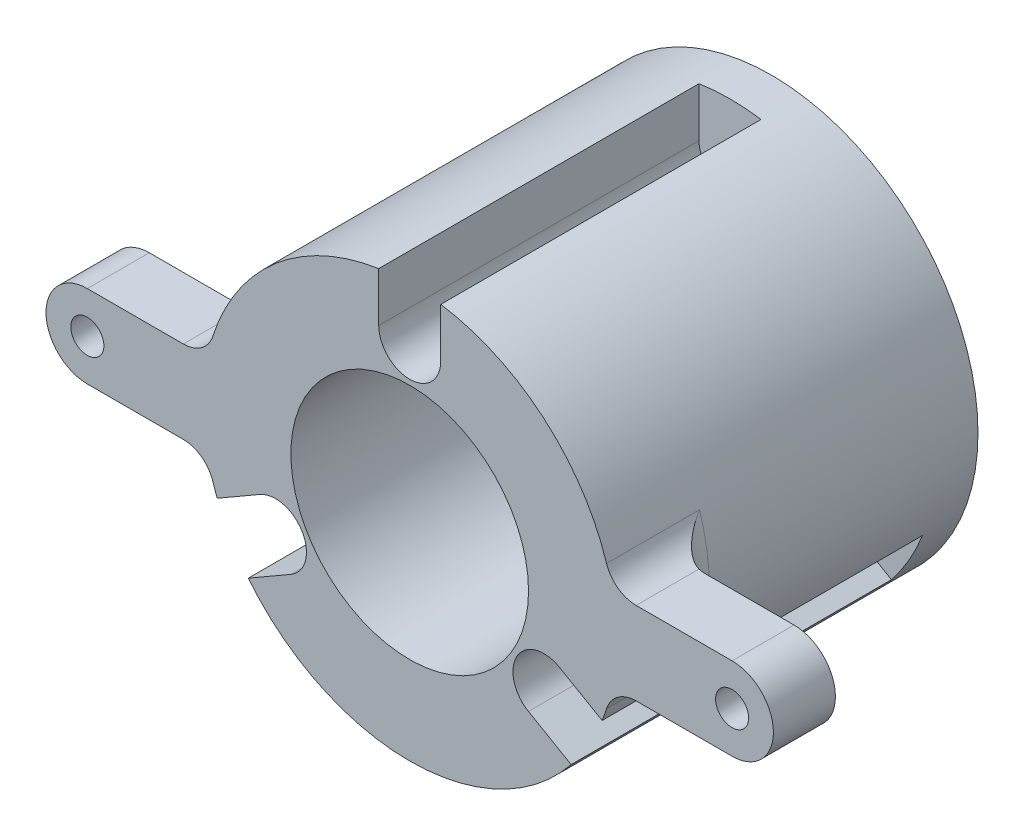
SolidWorks part; units mm, degrees
ref_plane "Front Plane" through (0, 0, 0) normal (0, 0, 1) x (1, 0, 0)
ref_plane "Top Plane" through (0, 0, 0) normal (0, 1, 0) x (1, 0, 0)
ref_plane "Right Plane" through (0, 0, 0) normal (1, 0, 0) x (0, 0, -1)
sketch "Sketch1" plane through (0, 0, 0) normal (0, 0, 1) x (1, 0, 0)
  line L0 (-3, 15) -> (-3, 19.7737)
  line L1 (3, 15) -> (3, 19.7737)
  line L2 (11.4904, -10.0981) -> (15.6245, -12.4849)
  line L3 (14.4904, -4.9019) -> (18.6245, -7.2888)
  line L4 (-14.4904, -4.9019) -> (-18.6245, -7.2888)
  line L5 (-11.4904, -10.0981) -> (-15.6245, -12.4849)
  circle A0 centre (0, 0) radius 10.5
  circle A2 centre (0, 15) radius 1.1
  circle A4 centre (0, 0) radius 20
  circle A7 centre (0, 15) radius 3
  circle A8 centre (12.9904, -7.5) radius 3
  circle A9 centre (12.9904, -7.5) radius 1.1
  circle A10 centre (-12.9904, -7.5) radius 3
  circle A11 centre (-12.9904, -7.5) radius 1.1
  point P26 (0, 0)
  dimension "D1" = 3
extrude "Boss-Extrude1" add sketch "Sketch1" along normal blind 35 contours A10 L5 A4 L2 A8 L3 L1 A7 L0 L4 A0 region at (0, 11.4359, 0)
extrude "Boss-Extrude2" add sketch "Sketch1<3>" along normal blind 4 contours A8 L2 A4 L3 | A8 A9 | A10 A11 | A10 L4 A4 L5 | A7 L1 A4 L0 | A7 A2 region at (0, 18.5541, 0) region at (0, 17.9151, 0) region at (-16.0683, -9.277, 0) region at (-11.5328, -4.9754, 0) region at (16.0683, -9.277, 0) region at (15.515, -6.0424, 0)
sketch "Sketch1<3>" plane through (0, 0, 0) normal (0, 0, 1) x (1, 0, 0) same geometry as "Sketch1"
sketch "Sketch2" plane through (0, 0, 35) normal (0, 0, 1) x (1, 0, 0)
  line L0 (0, 0) -> (31.2, 0) construction
  line L1 (31.2, 4) -> (19.5959, 4)
  line L2 (31.2, -4) -> (19.5959, -4)
  line L3 (0, 0) -> (0, 11.5) construction
  line L4 (-31.2, 4) -> (-19.5959, 4)
  line L5 (0, 0) -> (-31.2, 0) construction
  line L6 (-11.4904, -10.0981) -> (-15.6245, -12.4849)
  line L7 (15.6245, -12.4849) -> (11.4904, -10.0981)
  line L8 (14.4904, -4.9019) -> (18.6245, -7.2888)
  line L9 (3, 19.7737) -> (3, 15)
  line L10 (-3, 15) -> (-3, 19.7737)
  line L11 (-18.6245, -7.2888) -> (-14.4904, -4.9019)
  line L12 (-11.4904, -10.0981) -> (-15.6245, -12.4849)
  line L13 (15.6245, -12.4849) -> (11.4904, -10.0981)
  line L14 (14.4904, -4.9019) -> (18.6245, -7.2888)
  line L15 (3, 19.7737) -> (3, 15)
  line L16 (-3, 15) -> (-3, 19.7737)
  line L17 (-18.6245, -7.2888) -> (-14.4904, -4.9019)
  line L18 (-31.2, -4) -> (-19.5959, -4)
  circle A0 centre (31.2, 0) radius 1.6
  circle A1 centre (0, 0) radius 20
  circle A2 centre (0, 0) radius 11.5
  circle A3 centre (31.2, 0) radius 4
  circle A4 centre (-31.2, 0) radius 4
  circle A5 centre (-31.2, 0) radius 1.6
  arc A6 (-11.4904, -10.0981) -> (-14.4904, -4.9019) centre (-12.9904, -7.5) ccw
  arc A7 (-15.6245, -12.4849) -> (15.6245, -12.4849) centre (0, 0) ccw
  arc A8 (14.4904, -4.9019) -> (11.4904, -10.0981) centre (12.9904, -7.5) ccw
  arc A9 (18.6245, -7.2888) -> (3, 19.7737) centre (0, 0) ccw
  arc A10 (-3, 15) -> (3, 15) centre (0, 15) ccw
  arc A11 (-3, 19.7737) -> (-18.6245, -7.2888) centre (0, 0) ccw
  arc A12 (-11.4904, -10.0981) -> (-14.4904, -4.9019) centre (-12.9904, -7.5) ccw
  arc A13 (-15.6245, -12.4849) -> (15.6245, -12.4849) centre (0, 0) ccw
  arc A14 (14.4904, -4.9019) -> (11.4904, -10.0981) centre (12.9904, -7.5) ccw
  arc A15 (18.6245, -7.2888) -> (3, 19.7737) centre (0, 0) ccw
  arc A16 (-3, 15) -> (3, 15) centre (0, 15) ccw
  arc A17 (-3, 19.7737) -> (-18.6245, -7.2888) centre (0, 0) ccw
  point P39 (0, 0)
  arc M19 (18.6245, -7.2888) -> (3, 19.7737) centre (0, 0) ccw
  arc M23 (-3, 19.7737) -> (-18.6245, -7.2888) centre (0, 0) ccw
  circle M25 centre (0, 0) radius 10.5
  dimension "D2" = 2
  dimension "D1" = 0
extrude "Cut-Extrude1" cut sketch "Sketch2" against normal blind 30 contours A2 M25 region at (-11.1747, 0, 35)
extrude "Boss-Extrude3" add sketch "Sketch2<3>" against normal blind 6 contours A4 L18 L4 M23 | A4 A5 | A3 L1 L2 M19 | A3 A0 region at (24.0099, 0, 35) region at (33.9484, 2.7484, 35) region at (-24.0099, 0, 35) region at (-28.4516, 2.7484, 35)
sketch "Sketch2<3>" plane through (0, 0, 35) normal (0, 0, 1) x (1, 0, 0) same geometry as "Sketch2"
fillet "Fillet1" radius 3 6 edges at (19.5959, -4, 32) (20, 0, 29) (19.5959, 4, 32) (-19.5959, 4, 32) (-20, 0, 29) (-19.5959, -4, 32)
sketch "Sketch3" plane through (0, 0, 0) normal (0, 1, 0) x (1, 0, 0)
  line L0 (0, 0) -> (0, -13.5) construction
  circle A0 centre (0, -13.5) radius 3
extrude "Cut-Extrude2" cut sketch "Sketch3" against normal through all
